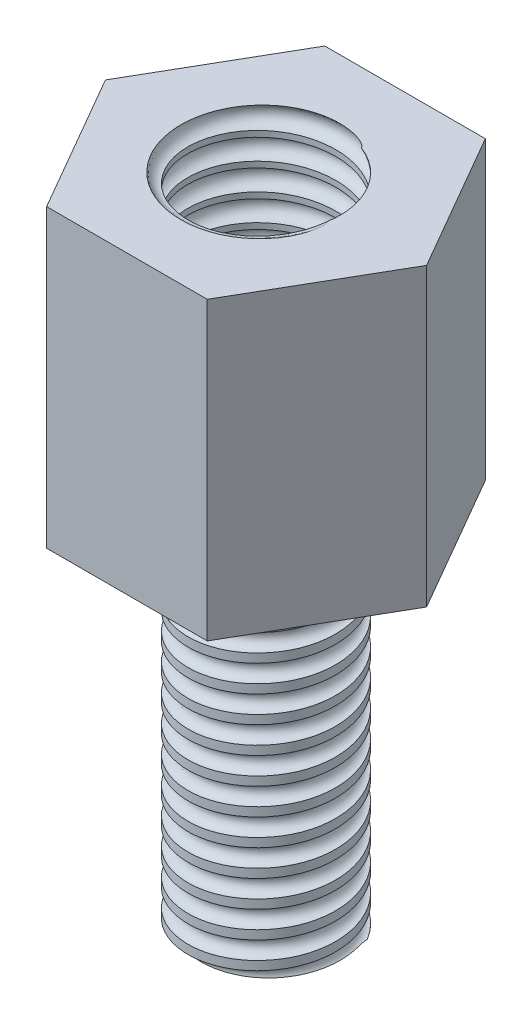
SolidWorks part; units mm, degrees
ref_plane "Front Plane" through (0, 0, 0) normal (0, 0, 1) x (1, 0, 0)
ref_plane "Top Plane" through (0, 0, 0) normal (0, 1, 0) x (1, 0, 0)
ref_plane "Right Plane" through (0, 0, 0) normal (1, 0, 0) x (0, 0, -1)
sketch "Sketch1" plane through (0, 0, 0) normal (0, 1, 0) x (1, 0, 0)
  line L1 (1.3568, -2.35) -> (2.7135, 0)
  line L2 (2.7135, 0) -> (1.3568, 2.35)
  line L3 (1.3568, 2.35) -> (-1.3568, 2.35)
  line L4 (-1.3568, 2.35) -> (-2.7135, 0)
  line L5 (-2.7135, 0) -> (-1.3568, -2.35)
  line L6 (-1.3568, -2.35) -> (1.3568, -2.35)
  circle A0 centre (0, 0) radius 2.35 construction
  point P1 (0, 2.35)
  dimension "D1" = 4.7
extrude "Boss-Extrude1" add sketch "Sketch1" along normal blind 8
sketch "Sketch2" plane through (0, 0, 0) normal (0, -1, 0) x (1, 0, 0)
  circle A0 centre (0, 0) radius 1.25
  dimension "D1" = 2.5
extrude "Boss-Extrude2" add sketch "Sketch2" along normal blind 6
sketch "Sketch4" plane through (0, -6, 0) normal (0, -1, 0) x (1, 0, 0)
  circle A0 centre (0, 0) radius 1.25 construction
  circle A1 centre (0, 0) radius 1.25
curve "Helix/Spiral1" pitch 0.45 height 5.9625 turns 13.25
sketch "Sketch5" plane through (0, 0, 0) normal (1, 0, 0) x (0, 0, -1)
  circle A0 centre (-1.25, -6) radius 0.15
  dimension "D1" = 0.3
sweep "Cut-Sweep3" cut profiles "Sketch5" path "Helix/Spiral1" align with end faces yes
sketch "Sketch9" plane through (0, 8, 0) normal (0, 1, 0) x (1, 0, 0)
  circle A0 centre (0, 0) radius 1.25
  dimension "D1" = 2.5
extrude "Cut-Extrude1" cut sketch "Sketch9" against normal blind 6
sketch "Sketch10" plane through (0, 8, 0) normal (0, 1, 0) x (1, 0, 0)
  circle A0 centre (0, 0) radius 1.25 construction
  circle A1 centre (0, 0) radius 1.25
curve "Helix/Spiral2" pitch 0.45 height 5.9625 turns 13.25
sketch "Sketch11" plane through (0, 0, 0) normal (1, 0, 0) x (0, 0, -1)
  circle A0 centre (1.25, 8) radius 0.175
  dimension "D1" = 0.35
sweep "Cut-Sweep4" cut profiles "Sketch11" path "Helix/Spiral2" align with end faces yes
sketch "Sketch12" plane through (0, 8, 0) normal (0, 1, 0) x (1, 0, 0)
  line L1 (3.4601, 3.0197) -> (-3.4601, 3.0197)
  line L2 (3.4601, 3.0197) -> (3.4601, -3.0197)
  line L3 (3.4601, -3.0197) -> (-3.4601, -3.0197)
  line L4 (-3.4601, 3.0197) -> (-3.4601, -3.0197)
  line L5 (3.4601, 3.0197) -> (-3.4601, -3.0197) construction
  line L6 (3.4601, -3.0197) -> (-3.4601, 3.0197) construction
  point P0 (0, 0)
extrude "Cut-Extrude2" cut sketch "Sketch12" against normal blind 3
